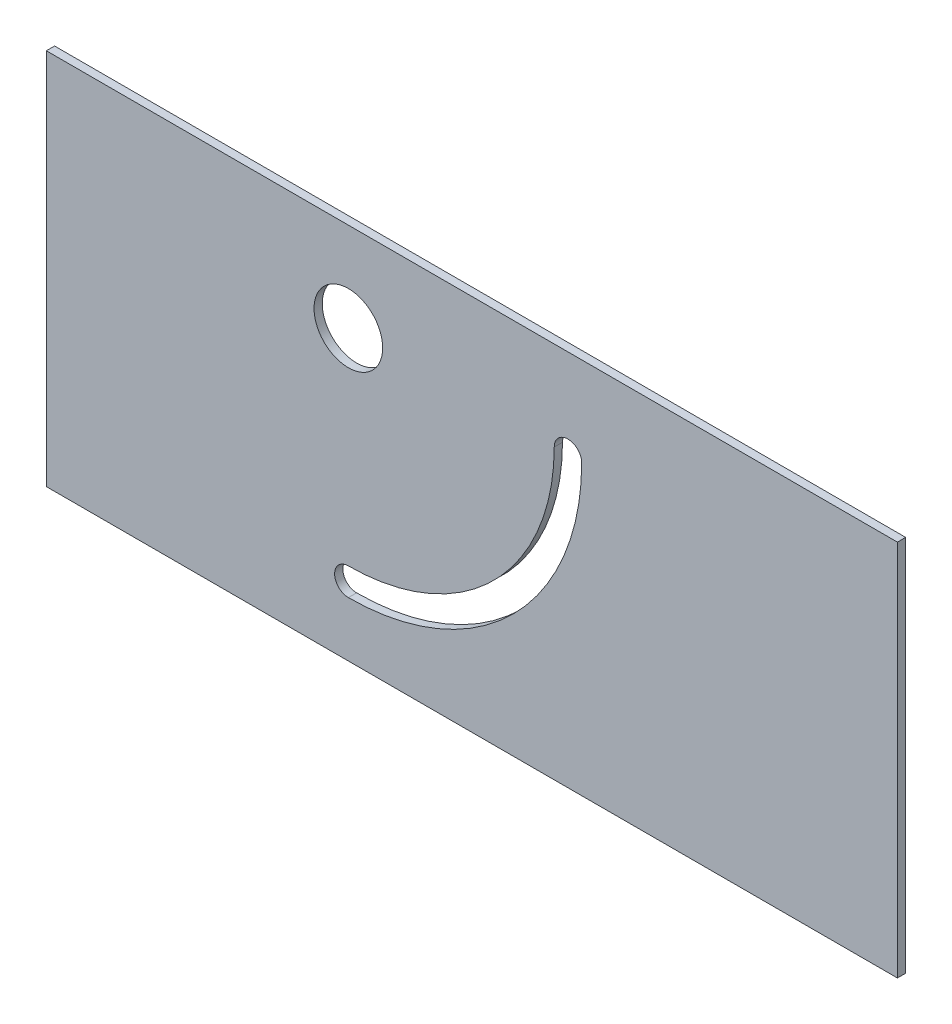
SolidWorks part; units mm, degrees
ref_plane "Front Plane" through (0, 0, 0) normal (0, 0, 1) x (1, 0, 0)
ref_plane "Top Plane" through (0, 0, 0) normal (0, 1, 0) x (1, 0, 0)
ref_plane "Right Plane" through (0, 0, 0) normal (1, 0, 0) x (0, 0, -1)
sketch "Sketch1" plane through (0, 0, 0) normal (0, 0, 1) x (1, 0, 0)
  line L1 (-25.5, 137.5) -> (284.5, 137.5)
  line L2 (-25.5, 137.5) -> (-25.5, 0)
  line L3 (-25.5, 0) -> (284.5, 0)
  line L4 (284.5, 137.5) -> (284.5, 0)
  line L5 (84.5, 59.75) -> (84.5, -77.75) construction
  arc A3 (169.5, 105) -> (159.5, 105) centre (164.5, 105) ccw
  arc A4 (159.5, 105) -> (84.5, 30) centre (84.5, 105) cw
  arc A5 (169.5, 105) -> (84.5, 20) centre (84.5, 105) cw
  arc A6 (84.5, 20) -> (84.5, 30) centre (84.5, 25) cw
  circle A7 centre (84.5, 105) radius 12.5
  point P3 (0, 0)
  point P4 (84.5, 119.1333)
  point P7 (84.5, 83.4155)
  point P8 (0, 0)
  point P10 (0, 0)
  dimension "D1" = 10
  dimension "D2" = 75
  dimension "D3" = 20
  dimension "D7" = 25
  dimension "D4" = 20
  dimension "D5" = 110
  dimension "D6" = 200
extrude "Boss-Extrude1" add sketch "Sketch1" along normal blind 3
